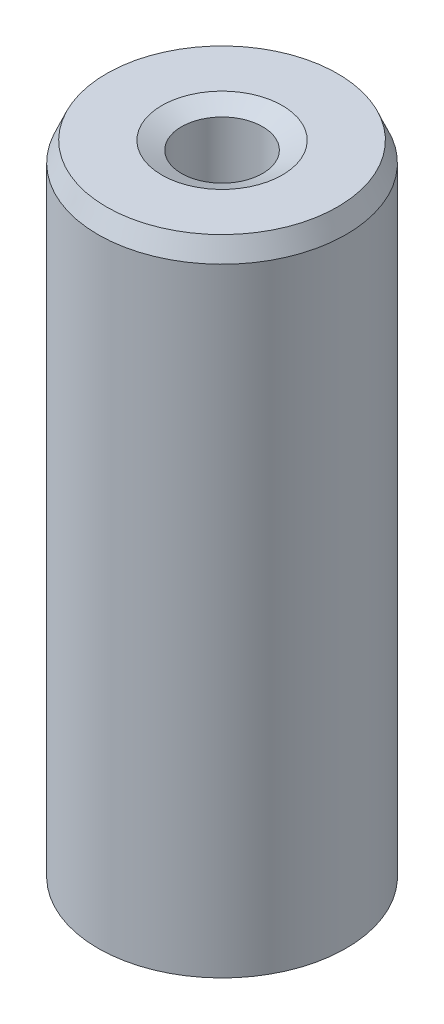
SolidWorks part; units mm, degrees
ref_plane "Front Plane" through (0, 0, 0) normal (0, 0, 1) x (1, 0, 0)
ref_plane "Top Plane" through (0, 0, 0) normal (0, 1, 0) x (1, 0, 0)
ref_plane "Right Plane" through (0, 0, 0) normal (1, 0, 0) x (0, 0, -1)
sketch "Sketch1" plane through (0, 0, 0) normal (0, 1, 0) x (1, 0, 0)
  circle A0 centre (0, 0) radius 5
  dimension "SLEEVE_OD" = 10
extrude "Boss-Extrude1" add sketch "Sketch1" along normal blind 26.0537
sketch "Sketch2" plane through (0, 0, 0) normal (0, 1, 0) x (1, 0, 0)
  circle A0 centre (0, 0) radius 1.6351
  dimension "BORE_D" = 3.2701
extrude "Cut-Extrude1" cut sketch "Sketch2" along normal through all
chamfer "Chamfer1" distance 0.7935 angle 23.344 4 edges at (0, 26.0537, 1.6351) (0, 0, 1.6351) (0, 0, 5) (0, 26.0537, 5) first distance on face at (0, 26.0537, 1.6351) first distance on face at (0, 0, 1.6351) first distance on face at (0, 26.0537, 5)
